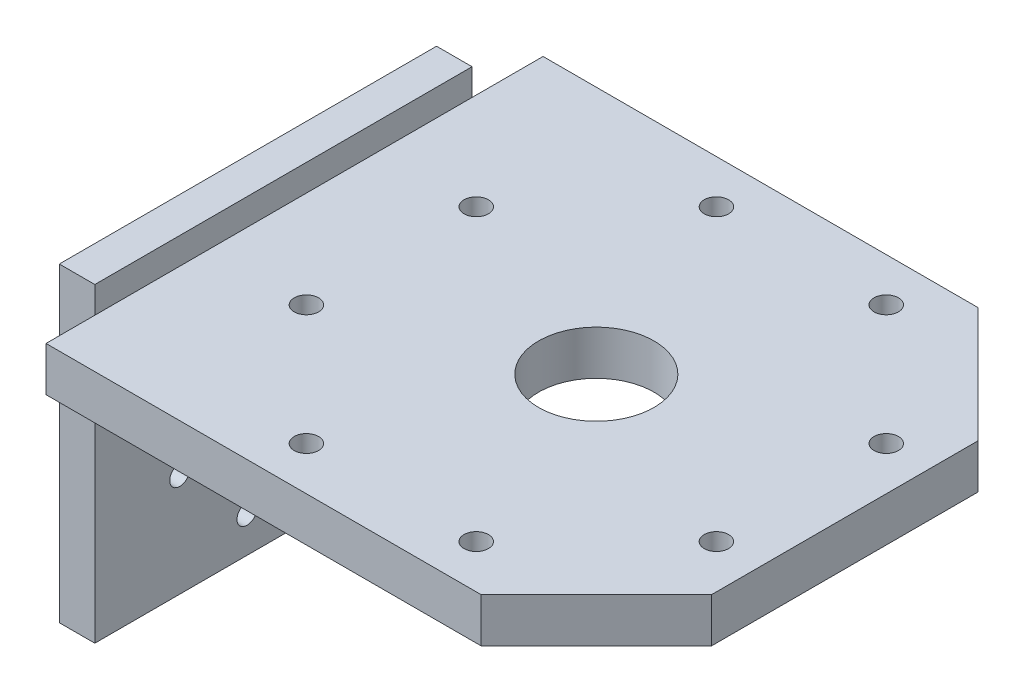
SolidWorks part; units mm, degrees
ref_plane "Front Plane" through (0, 0, 0) normal (0, 0, 1) x (1, 0, 0)
ref_plane "Top Plane" through (0, 0, 0) normal (0, 1, 0) x (1, 0, 0)
ref_plane "Right Plane" through (0, 0, 0) normal (1, 0, 0) x (0, 0, -1)
ref_plane "PL_Back_Plate_base" through (-76, 0, 0) normal (1, 0, 0) x (0, 0, -1)
sketch "SK_Back_Plate" plane through (-76, 0, 0) normal (1, 0, 0) x (0, 0, -1)
  line L0 (40, 36) -> (40, -34)
  line L1 (40, -34) -> (-45, -34)
  line L2 (-45, -34) -> (-45, 36)
  line L3 (-45, 36) -> (40, 36)
  circle A0 centre (25.8686, -10.7151) radius 2.25
  circle A1 centre (10.7151, -25.8686) radius 2.25
  circle A2 centre (-10.7151, -25.8686) radius 2.25
  circle A3 centre (-25.8686, -10.7151) radius 2.25
  circle A4 centre (-25.8686, 10.7151) radius 2.25
  circle A5 centre (-10.7151, 25.8686) radius 2.25
  circle A6 centre (10.7151, 25.8686) radius 2.25
  circle A7 centre (25.8686, 10.7151) radius 2.25
  circle A8 centre (0, 0) radius 6
  dimension "D9_SK_Back_Plate" = 4.5
  dimension "D12_SK_Back_Plate" = 4.5
  dimension "D15_SK_Back_Plate" = 4.5
  dimension "D18_SK_Back_Plate" = 4.5
  dimension "D21_SK_Back_Plate" = 4.5
  dimension "D24_SK_Back_Plate" = 4.5
  dimension "D27_SK_Back_Plate" = 4.5
  dimension "D30_SK_Back_Plate" = 4.5
  dimension "D33_SK_Back_Plate" = 12
  dimension "P1" = 40
  dimension "P2" = 36
  dimension "P3" = 40
  dimension "P4" = 34
  dimension "P5" = 45
  dimension "P6" = 34
  dimension "P7" = 45
  dimension "P8" = 36
  dimension "P10" = 25.8686
  dimension "P11" = 10.7151
  dimension "P13" = 10.7151
  dimension "P14" = 25.8686
  dimension "P16" = 10.7151
  dimension "P17" = 25.8686
  dimension "P19" = 25.8686
  dimension "P20" = 10.7151
  dimension "P22" = 25.8686
  dimension "P23" = 10.7151
  dimension "P25" = 10.7151
  dimension "P26" = 25.8686
  dimension "P28" = 10.7151
  dimension "P29" = 25.8686
  dimension "P31" = 25.8686
  dimension "P32" = 10.7151
extrude "Back_Plate" add sketch "SK_Back_Plate" along normal blind 8
ref_plane "PL_Roll_Pilot_Recess_base" through (-76, 0, 0) normal (1, 0, 0) x (0, 0, -1)
sketch "SK_Roll_Pilot_Recess" plane through (-76, 0, 0) normal (1, 0, 0) x (0, 0, -1)
  circle A0 centre (0, 0) radius 22.15
  dimension "D1_SK_Roll_Pilot_Recess" = 44.3
extrude "Roll_Pilot_Recess" cut sketch "SK_Roll_Pilot_Recess" along normal blind 2.2
ref_plane "PL_Medial_Plate_base" through (0, 20, 0) normal (0, 1, 0) x (1, 0, 0)
sketch "SK_Medial_Plate" plane through (0, 20, 0) normal (0, 1, 0) x (1, 0, 0)
  line L0 (-68, 56) -> (30, 56)
  line L1 (30, 56) -> (56, 30)
  line L2 (56, 30) -> (56, -30)
  line L3 (56, -30) -> (30, -56)
  line L4 (30, -56) -> (-68, -56)
  line L5 (-68, -56) -> (-68, 56)
  circle A0 centre (46.194, 19.1342) radius 2.75
  circle A1 centre (19.1342, 46.194) radius 2.75
  circle A2 centre (-19.1342, 46.194) radius 2.75
  circle A3 centre (-46.194, 19.1342) radius 2.75
  circle A4 centre (-46.194, -19.1342) radius 2.75
  circle A5 centre (-19.1342, -46.194) radius 2.75
  circle A6 centre (19.1342, -46.194) radius 2.75
  circle A7 centre (46.194, -19.1342) radius 2.75
  circle A8 centre (0, 0) radius 13
  dimension "D13_SK_Medial_Plate" = 5.5
  dimension "D16_SK_Medial_Plate" = 5.5
  dimension "D19_SK_Medial_Plate" = 5.5
  dimension "D22_SK_Medial_Plate" = 5.5
  dimension "D25_SK_Medial_Plate" = 5.5
  dimension "D28_SK_Medial_Plate" = 5.5
  dimension "D31_SK_Medial_Plate" = 5.5
  dimension "D34_SK_Medial_Plate" = 5.5
  dimension "D37_SK_Medial_Plate" = 26
  dimension "P1" = 68
  dimension "P2" = 56
  dimension "P3" = 30
  dimension "P4" = 56
  dimension "P5" = 56
  dimension "P6" = 30
  dimension "P7" = 56
  dimension "P8" = 30
  dimension "P9" = 30
  dimension "P10" = 56
  dimension "P11" = 68
  dimension "P12" = 56
  dimension "P14" = 46.194
  dimension "P15" = 19.1342
  dimension "P17" = 19.1342
  dimension "P18" = 46.194
  dimension "P20" = 19.1342
  dimension "P21" = 46.194
  dimension "P23" = 46.194
  dimension "P24" = 19.1342
  dimension "P26" = 46.194
  dimension "P27" = 19.1342
  dimension "P29" = 19.1342
  dimension "P30" = 46.194
  dimension "P32" = 19.1342
  dimension "P33" = 46.194
  dimension "P35" = 46.194
  dimension "P36" = 19.1342
extrude "Medial_Plate" add sketch "SK_Medial_Plate" along normal blind 10
equation "\"Roll_face_x\" = -76"
equation "\"Pitch_rear_y\" = -20"
equation "\"Plate_t\" = 10"
equation "\"Back_bottom_z\" = -40"
